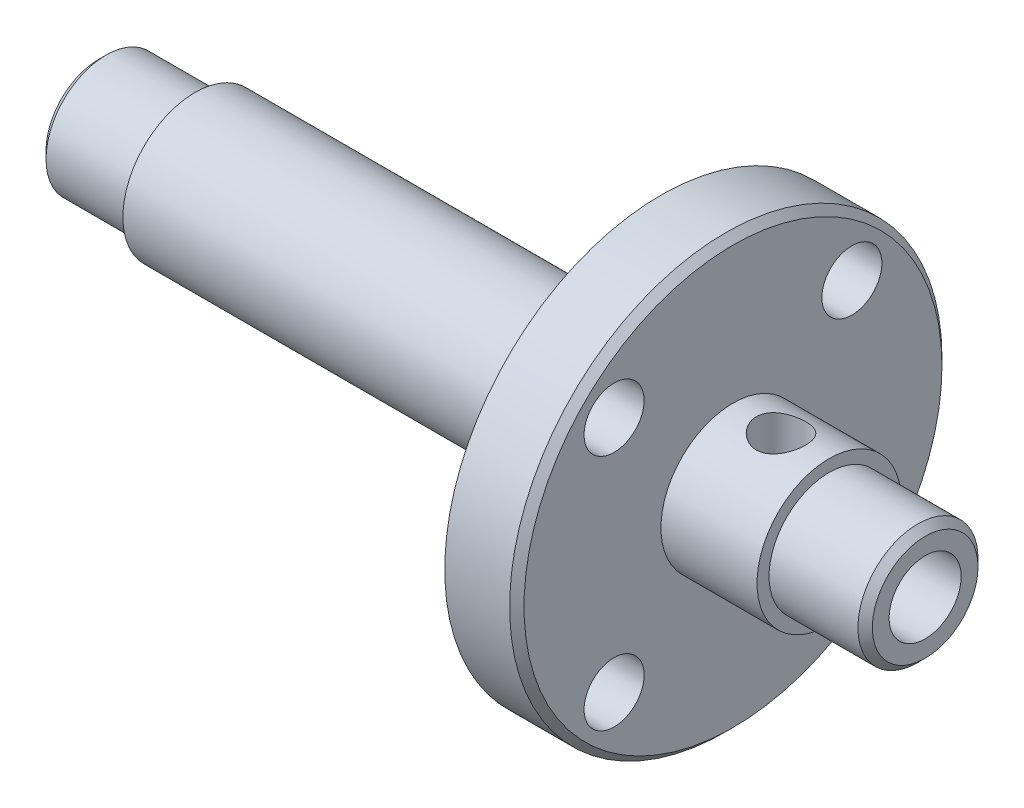
SolidWorks part; units mm, degrees
material "6061-T6 (SS)"
ref_plane "前视基准面" through (0, 0, 0) normal (0, 0, 1) x (1, 0, 0)
ref_plane "上视基准面" through (0, 0, 0) normal (0, 1, 0) x (1, 0, 0)
ref_plane "右视基准面" through (0, 0, 0) normal (1, 0, 0) x (0, 0, -1)
ref_axis "基准轴1" through (21.711, 0, 0) along (1, 0, 0)
sketch "草图1" plane through (0, 0, 0) normal (0, 0, 1) x (1, 0, 0)
  line L0 (0, 0) -> (0, 2.5)
  line L1 (0, 2.5) -> (4, 2.5)
  line L2 (4, 2.5) -> (4, 3)
  line L3 (4, 3) -> (23.4, 3)
  line L4 (23.4, 3) -> (23.4, 9)
  line L5 (23.4, 9) -> (26.4, 9)
  line L6 (26.4, 9) -> (26.4, 3)
  line L7 (26.4, 3) -> (30.4, 3)
  line L8 (30.4, 3) -> (30.4, 2.5)
  line L9 (30.4, 2.5) -> (34.4, 2.5)
  line L14 (34.4, 2.5) -> (34.4, 0)
  line L15 (34.4, 0) -> (0, 0)
  dimension "D1" = 4
  dimension "D2" = 2.5
  dimension "D3" = 3
  dimension "D4" = 19.4
  dimension "D5" = 9
  dimension "D6" = 3
  dimension "D7" = 3
  dimension "D8" = 2.5
  dimension "D9" = 4
  dimension "D10" = 4
revolve "旋转1" add sketch "草图1" angle 360 about L15
sketch "草图2" plane through (26.4, 0, 0) normal (1, 0, 0) x (0, 0, -1)
  line L0 (-4.9497, -4.9497) -> (-4.9497, 4.9497) construction
  line L1 (-4.9497, -4.9497) -> (4.9497, -4.9497) construction
  line L2 (-4.9497, 4.9497) -> (4.9497, 4.9497) construction
  line L3 (4.9497, -4.9497) -> (4.9497, 4.9497) construction
  line L4 (-4.9497, -4.9497) -> (4.9497, 4.9497) construction
  line L5 (-4.9497, 4.9497) -> (4.9497, -4.9497) construction
  circle A0 centre (0, 0) radius 7 construction
  circle A1 centre (4.9497, 4.9497) radius 1.5
  circle A2 centre (-4.9497, -4.9497) radius 1.5
  circle A3 centre (-4.9497, 4.9497) radius 1.5
  circle A4 centre (4.9497, -4.9497) radius 1.5
  dimension "D1" = 14
  dimension "D2" = 3
hole_wizard "M3 螺纹孔1" positions "3D草图1" profile "草图3" tap size "M3" standard "GB" end condition through all
sketch3d "3D草图1"
  circle A0 centre (26.4, 0, 0) radius 7 construction
  point P0 (26.4, 4.9497, 4.9497)
  point P4 (33.4, 0, 0)
  point P5 (26.4, 4.9497, -4.9497)
  point P7 (26.4, -4.9497, -4.9497)
  point P10 (26.4, -4.9497, 4.9497)
sketch "草图3" plane through (26.4, 4.9497, 4.9497) normal (0, 1, 0) x (0, 0, -1)
  line L0 (0, 0) -> (0, 26.4)
  line L1 (0, 26.4) -> (1.25, 26.4)
  line L2 (1.25, 26.4) -> (1.25, 0)
  line L5 (1.25, 0) -> (0, 0)
  line L11 (0, -6.35) -> (0, 107.95) construction
  dimension "通孔螺纹孔钻头直径" = 2.5
  dimension "通孔螺纹孔钻头深度" = 26.4
cosmetic thread "孔螺蚊线1"
cosmetic thread "孔螺蚊线2"
cosmetic thread "孔螺蚊线3"
cosmetic thread "孔螺蚊线4"
sketch "草图4" plane through (34.4, 0, 0) normal (-1, 0, 0) x (0, 0, 1)
  circle A0 centre (0, 0) radius 1.5
  dimension "D1" = 3
extrude "切除-拉伸1" [suppressed] cut sketch "草图4" along normal blind 10
ref_plane "基准面1" through (0, 3, 0) normal (0, 1, 0) x (1, 0, 0)
sketch "草图5" plane through (0, 3, 0) normal (0, 1, 0) x (1, 0, 0)
  line L0 (30.4, 0) -> (26.4, 0) construction
  line L1 (30.4, -3) -> (30.4, 3) construction
  line L2 (26.4, -9) -> (26.4, 9) construction
  circle A0 centre (28.4, 0) radius 1.25
  dimension "D1" = 2.5
hole_wizard "M2.5 螺纹孔1" positions "3D草图2" profile "草图6" tap size "M2.5" standard "GB"
sketch3d "3D草图2"
  point P3 (28.4, 3, 0)
cosmetic thread "孔螺蚊线6"
sketch "草图6" plane through (28.4, 3, 0) normal (1, 0, 0) x (0, 0, 1)
  line L0 (0, 0) -> (0, 4.3659)
  line L1 (0, 4.3659) -> (1.025, 3.75)
  line L2 (1.025, 3.75) -> (1.025, 0)
  line L5 (1.025, 0) -> (0, 0)
  line L10 (0, 4.3659) -> (-1.025, 3.75) construction
  line L11 (0, -6.35) -> (0, 107.95) construction
  dimension "螺纹孔钻头直径" = 2.05
  dimension "螺纹孔钻头深度" = 3.75
  dimension "导头角度" = 118
chamfer "倒角1" distance 0.3 angle 45 3 edges at (34.4, 0, -2.5) (0, 0, -2.5) (26.4, 0, -9)
hole_wizard "大小mm 暗销孔1" positions "3D草图3" profile "草图7" hole size "Ø3.0" standard "ISO"
sketch3d "3D草图3"
  point P0 (34.4, 0, 0)
sketch "草图7" plane through (34.4, 0, 0) normal (0, 1, 0) x (0, 0, -1)
  line L0 (0, 0) -> (0, 10.9013)
  line L1 (0, 10.9013) -> (1.5, 10)
  line L2 (1.5, 10) -> (1.5, 0)
  line L5 (1.5, 0) -> (0, 0)
  line L10 (0, 10.9013) -> (-1.5, 10) construction
  line L11 (0, -6.35) -> (0, 107.95) construction
  dimension "孔直径" = 3
  dimension "孔深度" = 10
  dimension "导头角度" = 118
